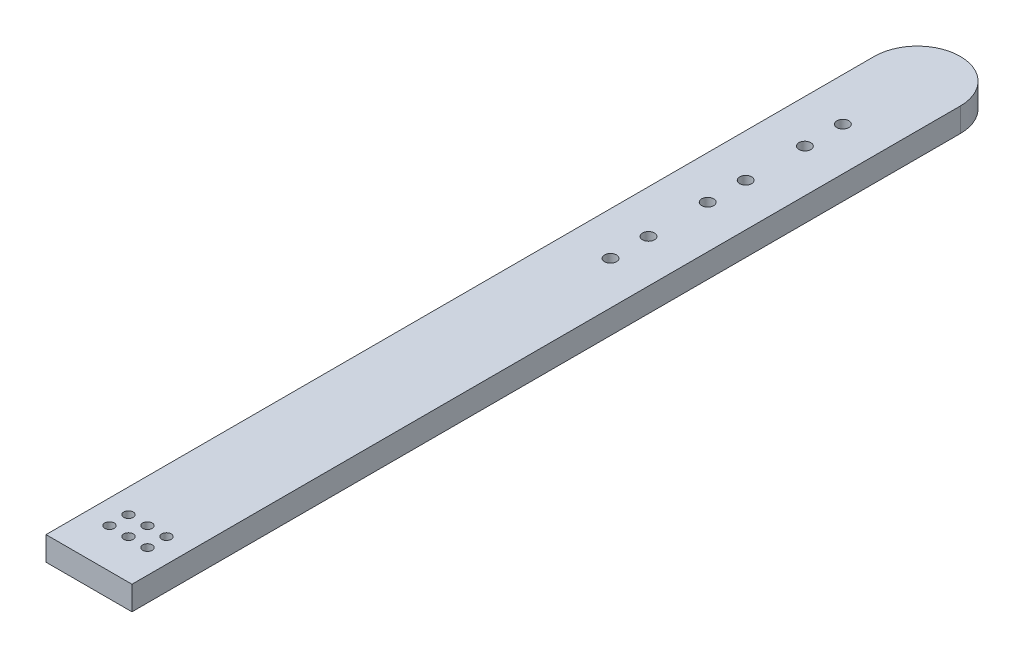
SolidWorks part; units mm, degrees
ref_plane "Front Plane" through (0, 0, 0) normal (0, 0, 1) x (1, 0, 0)
ref_plane "Top Plane" through (0, 0, 0) normal (0, 1, 0) x (1, 0, 0)
ref_plane "Right Plane" through (0, 0, 0) normal (1, 0, 0) x (0, 0, -1)
sketch "Sketch1" plane through (0, 0, 0) normal (0, 1, 0) x (1, 0, 0)
  line L0 (0, 0) -> (0, 35.2425) construction
  line L1 (-2.875, 0) -> (-2.875, 35.2425)
  line L2 (2.875, 0) -> (2.875, 35.2425)
  line L3 (-2.875, 0) -> (2.875, 0)
  line L6 (2.875, 0) -> (-2.875, 0)
  line L7 (2.875, 0) -> (2.875, -20.1575)
  line L8 (2.875, -20.1575) -> (-2.875, -20.1575)
  line L9 (-2.875, 0) -> (-2.875, -20.1575)
  line L10 (-10.6594, -20.1575) -> (-7.8276, -20.1575) construction
  arc A0 (-2.875, 0) -> (2.875, 0) centre (0, 0) ccw
  arc A1 (2.875, 35.2425) -> (-2.875, 35.2425) centre (0, 35.2425) ccw
  point P3 (0, 17.6212)
  point P10 (0, 38.1175)
  dimension "D1" = 5.75
extrude "Boss-Extrude1" add sketch "Sketch1" along normal blind 1.6 contours L2 A1 L1 L3 | A0 L9 L8 L7 | L3 A0 L6 region at (0, 0, -18.7557) region at (0, 0, 11.1963) region at (0, 0, 1.2202)
ref_axis "Axis1" through (0, 1.6, -35.2425) along (0, -1, 0)
sketch "Sketch2" plane through (0, 0, 0) normal (0, -1, 0) x (1, 0, 0)
  line L0 (-2.875, 20.1575) -> (-2.875, -35.2425) construction
  line L1 (-2.875, 20.1575) -> (-2.875, -35.2425)
  line L2 (2.875, 20.1575) -> (-2.875, 20.1575) construction
  line L3 (2.875, 20.1575) -> (-2.875, 20.1575)
  circle A0 centre (1.27, 16.2459) radius 0.3175
  circle A1 centre (0, 16.2459) radius 0.3175
  circle A2 centre (-1.27, 16.2459) radius 0.3175
  circle A3 centre (0, 17.5159) radius 0.3175
  circle A4 centre (-1.27, 17.5159) radius 0.3175
  circle A5 centre (1.27, 17.5159) radius 0.3175
  circle A6 centre (0, -30.2625) radius 0.4
  circle A10 centre (0, -23.7625) radius 0.4
  circle A11 centre (0, -17.2625) radius 0.4
  arc A12 (-2.0248, -33.6925) -> (2.0248, -33.6925) centre (0, -35.2425) ccw construction
  arc A13 (-2.875, -35.2425) -> (2.875, -35.2425) centre (0, -35.2425) ccw construction
  arc A14 (-2.875, -35.2425) -> (2.875, -35.2425) centre (0, -35.2425) ccw
  circle A15 centre (1.4441, -30.2625) radius 0.4 [skipped]
  circle A16 centre (1.4441, -23.7625) radius 0.4 [skipped]
  circle A17 centre (1.4441, -17.2625) radius 0.4 [skipped]
  circle A18 centre (0, -27.7225) radius 0.4
  circle A19 centre (0, -21.2225) radius 0.4
  circle A20 centre (0, -14.7225) radius 0.4
  point P15 (0, -35.2425)
  dimension "D1" = 0.635
  dimension "D4" = 0.8
  dimension "D7" = 4.98
  dimension "D8" = 2.875
  dimension "D9" = 55.4
  dimension "D10" = 51.4884
  dimension "D11" = 1.27
  dimension "D12" = 2.54
  dimension "D14" = 2.54
  dimension "D15" = 11.48
  dimension "D16" = 17.98
  dimension "D2" = 3
  dimension "D3" = 2
  dimension "D5" = 2
  dimension "D6" = 3
  dimension "D13" = 3
extrude "Cut-Extrude1" cut sketch "Sketch2" against normal through all contours A18 | A6 | A10 | A11 | A5 | A0 | A1 | A3 | A2 | A4 | A20 | A19
